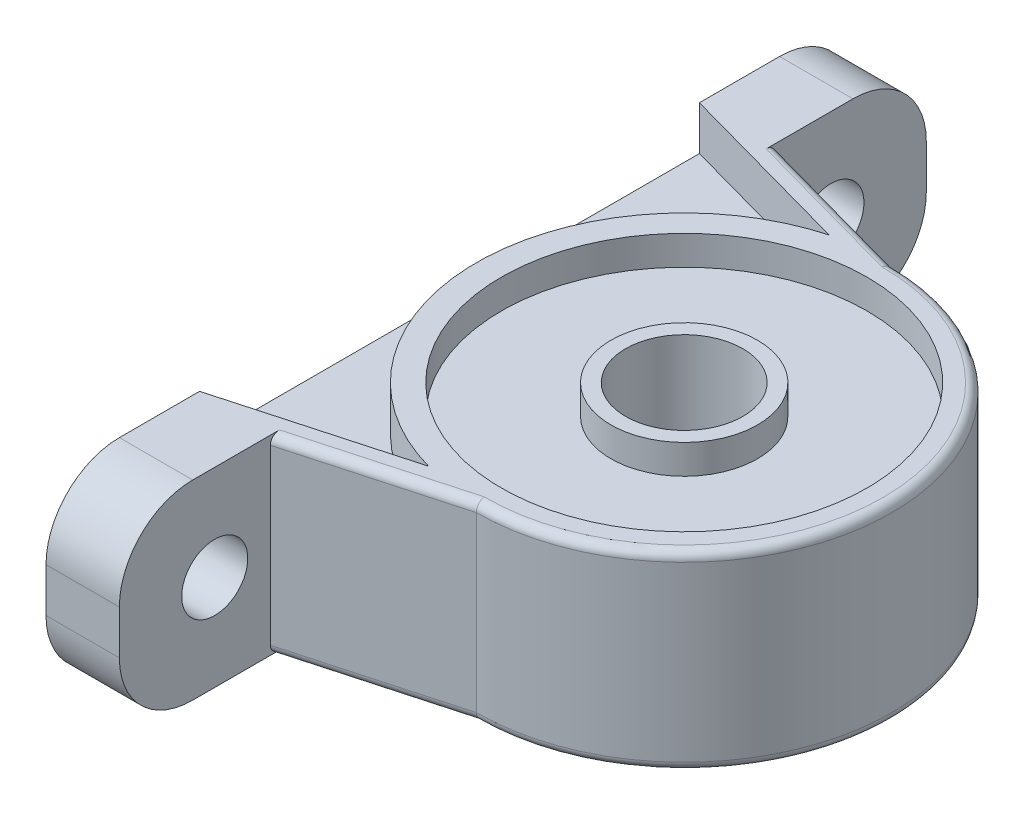
SolidWorks part; units mm, degrees
ref_plane "Спереди" through (0, 0, 0) normal (0, 0, 1) x (1, 0, 0)
ref_plane "Сверху" through (0, 0, 0) normal (0, 1, 0) x (1, 0, 0)
ref_plane "Справа" through (0, 0, 0) normal (1, 0, 0) x (0, 0, -1)
sketch "Эскиз1" plane through (0, 0, 0) normal (0, 1, 0) x (1, 0, 0)
  line L0 (0, 31.3474) -> (0, -36.1634) construction
  line L1 (-16, 27.5) -> (-16, -27.5)
  line L2 (-16, -27.5) -> (-11, -27.5)
  line L3 (-11, -27.5) -> (-11, -17.2068)
  line L4 (-11, -17.2068) -> (0, -14.1623)
  line L5 (-16, 0) -> (0, 0) construction
  line L6 (-16, 27.5) -> (-11, 27.5)
  line L7 (-11, 17.2068) -> (0, 14.1623)
  line L8 (-11, 27.5) -> (-11, 17.2068)
  circle A0 centre (0, 0) radius 12.459
  circle A1 centre (0, 0) radius 4
  circle A2 centre (0, 0) radius 5
  circle A3 centre (0, 0) radius 14.1623
  dimension "D4" = 8
  dimension "D5" = 10
  dimension "D6" = 24.918
  dimension "D7" = 28.3245
  dimension "D1" = 27.5
  dimension "D2" = 16
  dimension "D3" = 5
  dimension "D8" = 10.2932
extrude "Бобышка-Вытянуть1" add sketch "Эскиз1" along normal blind 13 contours A3 L7 L8 L6 L1 L2 L3 L4 | A3 A0 | A2 A1 region at (-13.5, 0, -26.9272) region at (9.731, 0, -9.731) region at (-4.8586, 0, 0)
extrude "Бобышка-Вытянуть2" add sketch "Эскиз1<3>" along normal blind 9 from offset 2 contours A0 A2 region at (-12.1066, 0, 0)
sketch "Эскиз1<3>" plane through (0, 0, 0) normal (0, 1, 0) x (1, 0, 0) same geometry as "Эскиз1"
sketch "Эскиз2" plane through (-11, 0, 0) normal (1, 0, 0) x (0, 0, -1)
  line L0 (27.5, 13) -> (27.5, 0) construction
  line L1 (27.5, 13) -> (-27.5, 13) construction
  circle A0 centre (21, 6.5) radius 2.25
  circle A1 centre (-21, 6.5) radius 2.25
  point P9 (27.5, 6.5)
  point P14 (0, 13)
  dimension "D1" = 4.5
  dimension "D2" = 42
  dimension "D3" = 21
extrude "Вырез-Вытянуть1" cut sketch "Эскиз2" against normal blind 9
fillet "Скругление1" radius 5 4 edges at (-13.5, 0, 27.5) (-13.5, 13, 27.5) (-13.5, 13, -27.5) (-13.5, 0, -27.5)
sketch "Эскиз3" plane through (0, 0, 0) normal (0, -1, 0) x (1, 0, 0)
  circle A0 centre (0, 0) radius 5
  circle A1 centre (0, 0) radius 4
  dimension "D1" = 10
  dimension "D2" = 8
extrude "Бобышка-Вытянуть3" add sketch "Эскиз3" along normal blind 3
sketch "Эскиз4" plane through (0, 0, 0) normal (0, -1, 0) x (1, 0, 0)
  line L0 (-16, -17.0343) -> (-3.7735, -13.6503)
  line L1 (-16, -22.5) -> (-16, 22.5) construction
  line L2 (0, 0) -> (-25.5469, 0) construction
  line L3 (-16, -17.0343) -> (-16, 17.0343)
  line L4 (-11, -17.2068) -> (0, -14.1623) construction
  line L5 (-16, 17.0343) -> (-3.7735, 13.6503)
  circle A0 centre (0, 0) radius 14.1623
  arc A1 (0, -14.1623) -> (0, 14.1623) centre (0, 0) ccw construction
  point P15 (-16, 0)
  line M6 (-16, 22.5) -> (-16, -22.5)
  dimension "D1" = 1.5
extrude "Вырез-Вытянуть2" cut sketch "Эскиз4" against normal blind 3 contours A0 L2 L3 L0 | L2 A0 L5 M6 region at (-12.6593, 0, -10.469) region at (-12.6593, 0, 10.469)
ref_plane "Плоскость1" [suppressed] through (0, 6.5, 0) normal (0, 1, 0) x (1, 0, 0)
mirror "Зеркальное отражение1" about plane through (0, 6.5, 0) normal (0, 1, 0) of "Вырез-Вытянуть2"
fillet "Скругление2" radius 0.6 6 edges at (-5.5, 13, 15.6846) (-5.5, 13, -15.6846) (14.1623, 13, 0) (-5.5, 0, 15.6846) (-5.5, 0, -15.6846) (14.1623, 0, 0)
